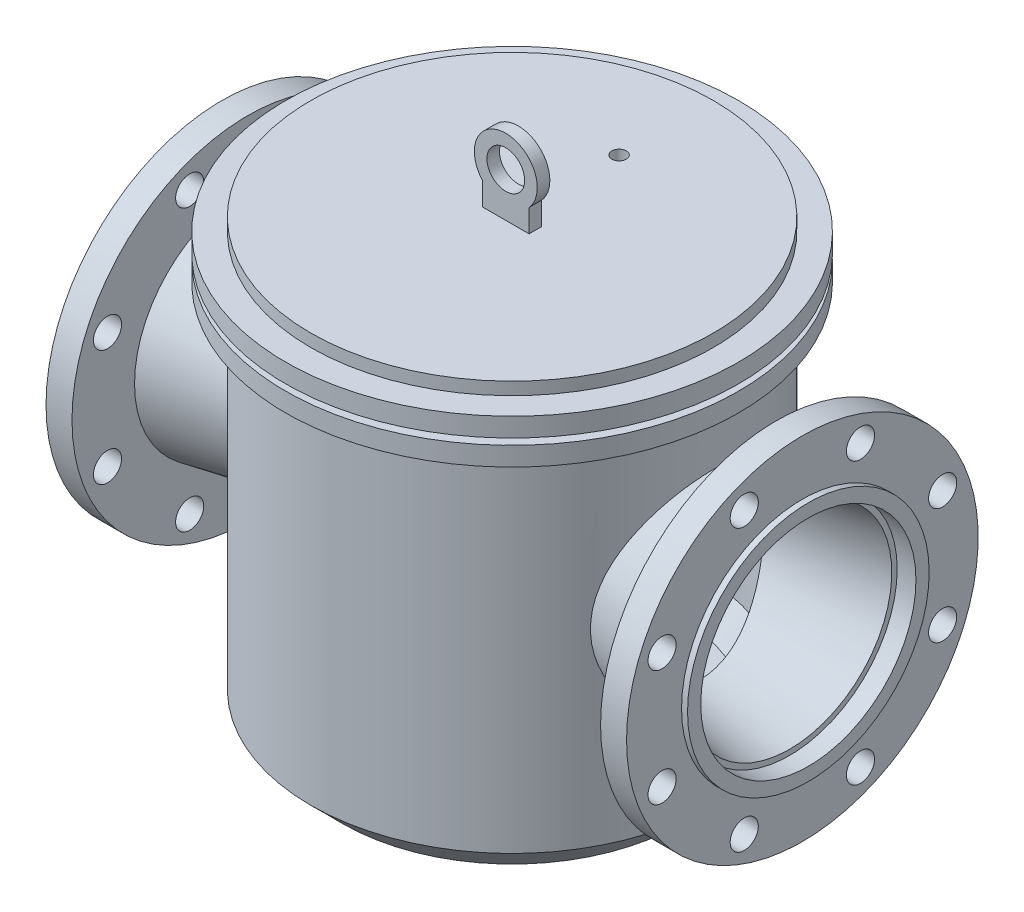
SolidWorks part; units mm, degrees
material "Cast Stainless Steel"
ref_plane "Front" through (0, 0, 0) normal (0, 0, 1) x (1, 0, 0)
ref_plane "Top" through (0, 0, 0) normal (0, 1, 0) x (1, 0, 0)
ref_plane "Right" through (0, 0, 0) normal (1, 0, 0) x (0, 0, -1)
other "Configuration Table"
sketch "Sketch1" plane through (0, 0, 0) normal (0, 0, 1) x (1, 0, 0)
  line L0 (0, -64.0794) -> (0, 96.1191) construction
  line L1 (0, -185) -> (50, -185)
  line L2 (50, -185) -> (50, -175)
  line L3 (50, -175) -> (135, -175)
  line L4 (135, -175) -> (160, -150)
  line L5 (160, -150) -> (160, 175)
  line L6 (160, 175) -> (0, 175)
  line L8 (0, 0) -> (119.9736, 0) construction
  line L15 (0, -185) -> (0, 175)
  dimension "D1" = 160
  dimension "D2" = 175
  dimension "D3" = 175
  dimension "D4" = 25
  dimension "D5" = 135
  dimension "D6" = 50
  dimension "D7" = 10
revolve "Base-Revolve" add sketch "Sketch1" angle 360 about L0
sketch "Sketch2" plane through (0, 0, 0) normal (0, 0, 1) x (1, 0, 0)
  line L0 (160, -150) -> (160, 175) construction
  line L1 (160, 165) -> (180, 165)
  line L2 (160, 165) -> (160, 150)
  line L3 (160, 150) -> (180, 150)
  line L4 (180, 165) -> (180, 150)
  line L5 (160, 145) -> (180, 145)
  line L6 (160, 145) -> (160, 130)
  line L7 (160, 130) -> (180, 130)
  line L8 (180, 145) -> (180, 130)
  line L9 (160, 175) -> (-160, 175) construction
  line L10 (0, 0) -> (0, 185.8464) construction
  dimension "D1" = 15
  dimension "D2" = 5
  dimension "D3" = 20
  dimension "D4" = 10
revolve "Boss-Revolve1" add sketch "Sketch2" angle 360 about L10
sketch "Sketch3" plane through (0, 0, 0) normal (0, 0, 1) x (1, 0, 0)
  line L0 (0, 0) -> (283.0144, 0) construction
  line L1 (0, 0) -> (0, 52.9713)
  line L2 (0, -64.0794) -> (0, 96.1191) construction
  line L3 (0, 52.9713) -> (210, 90)
  line L4 (210, 90) -> (210, 139.7)
  line L5 (210, 139.7) -> (230.65, 139.7)
  line L6 (230.65, 139.7) -> (230.65, 96)
  line L7 (230.65, 96) -> (235.4, 96)
  line L8 (235.4, 96) -> (235.4, 0)
  line L9 (235.4, 0) -> (0, 0)
  dimension "D1" = 210
  dimension "D2" = 96
  dimension "D3" = 4.75
  dimension "D4" = 20.65
  dimension "D5" = 139.7
  dimension "D6" = 90
  dimension "D7" = 100
revolve "Boss-Revolve2" add sketch "Sketch3" angle 360 about L0
mirror "Mirror1" about plane through (0, 0, 0) normal (1, 0, 0) of "Boss-Revolve2"
shell "Shell1" thickness 10.5 removed face at (235.4, 0, 96) removed face at (-235.4, 0, 96)
sketch "Sketch5" plane through (230.65, 0, 0) normal (1, 0, 0) x (0, 0, -1)
  line L1 (0, 0) -> (0, 158.3439) construction
  line L2 (0, 0) -> (-46.1708, 111.4661) construction
  circle A0 centre (-46.1708, 111.4661) radius 11.175
  dimension "D1" = 22.35
  dimension "D2" = 120.65
  dimension "D3" = 22.5
extrude "Cut-Extrude1" cut sketch "Sketch5" against normal up to next
pattern_circular "CirPattern1" count 8 over 360 about axis through (0, 0, 0) along (1, 0, 0) of "Cut-Extrude1"
sketch "Sketch6" plane through (-230.65, 0, 0) normal (-1, 0, 0) x (0, 0, 1)
  circle A0 centre (46.1708, 111.4661) radius 11.175 construction
  circle A1 centre (46.1708, 111.4661) radius 11.175
extrude "Cut-Extrude2" cut sketch "Sketch6" against normal up to next
pattern_circular "CirPattern3" count 8 over 360 about axis through (0, 0, 0) along (1, 0, 0) of "Cut-Extrude2"
sketch "Sketch7" plane through (0, 0, 0) normal (0, 0, 1) x (1, 0, 0)
  line L0 (0, 0) -> (0, 290.4191) construction
  line L1 (0, 164.5) -> (0, -145.6508) construction
  line L2 (-18.5, 175) -> (18.5, 175)
  line L3 (18.5, 175) -> (18.5, 193.1848)
  line L4 (-18.5, 175) -> (-18.5, 193.1848)
  line L5 (160, 175) -> (-160, 175) construction
  arc A0 (-18.5, 193.1848) -> (18.5, 193.1848) centre (0, 210) cw
  circle A1 centre (0, 210) radius 15
  point P8 (0, 175)
  dimension "D1" = 25
  dimension "D2" = 30
  dimension "D3" = 37
  dimension "D4" = 35
extrude "Boss-Extrude1" add sketch "Sketch7" along normal mid plane 10
hole_wizard "1/2-20 Tapped Hole1" positions "3DSketch1" profile "Sketch8" tap size "1/2-20" standard "Ansi Inch" end condition up to next
sketch3d "3DSketch1"
  point P0 (0, 175, -85)
  dimension "D1" = 80
  dimension "D2" = 210
sketch "Sketch8" plane through (0, 175, -85) normal (1, 0, 0) x (0, 0, 1)
  line L0 (0, 0) -> (0, 10.5)
  line L1 (0, 10.5) -> (5.7544, 10.5)
  line L2 (5.7544, 10.5) -> (5.7544, 0)
  line L5 (5.7544, 0) -> (0, 0)
  line L11 (0, -6.35) -> (0, 107.95) construction
  dimension "Thru Tap Drill Dia." = 11.5087
  dimension "Thru Tap Drill Depth" = 10.5
cosmetic thread "Hole Thread1" parameters "D2"=12.7
